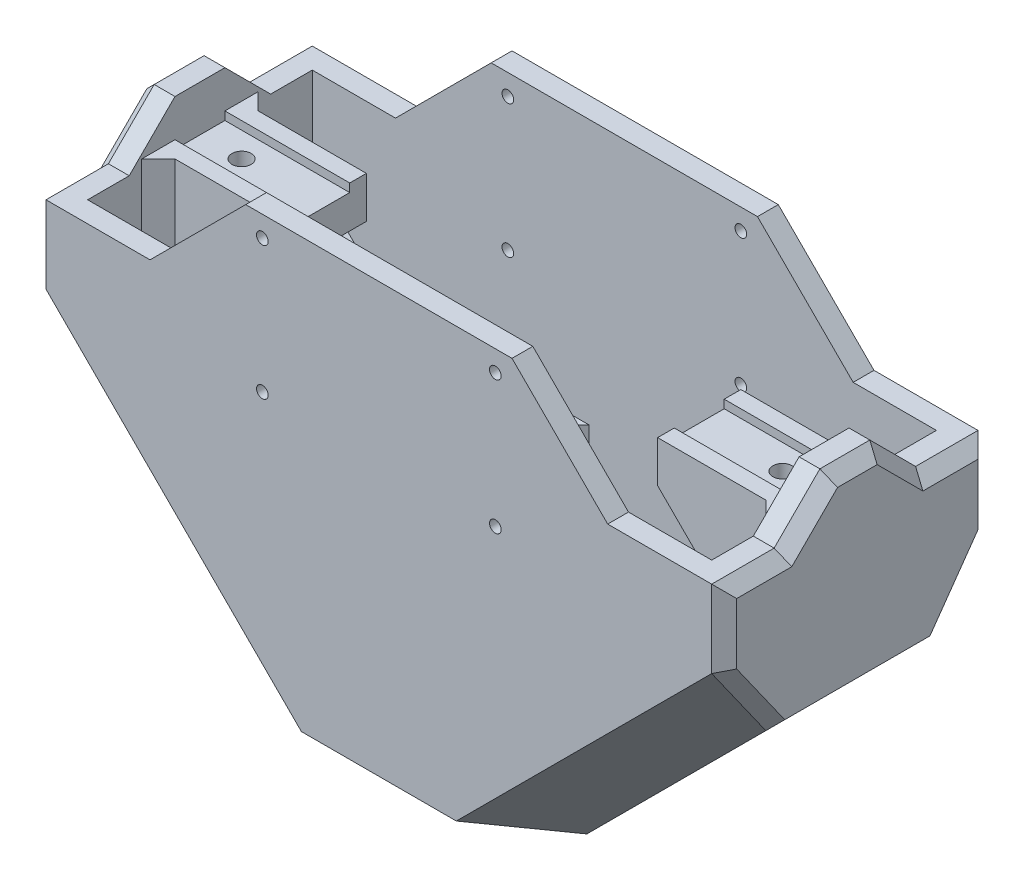
SolidWorks part; units mm, degrees
ref_plane "Front Plane" through (0, 0, 0) normal (0, 0, 1) x (1, 0, 0)
ref_plane "Top Plane" through (0, 0, 0) normal (0, 1, 0) x (1, 0, 0)
ref_plane "Right Plane" through (0, 0, 0) normal (1, 0, 0) x (0, 0, -1)
sketch "Sketch1" plane through (0, 0, 0) normal (0, 1, 0) x (1, 0, 0)
  line L1 (-75, -27) -> (75, -27)
  line L2 (-75, -27) -> (-75, 27)
  line L3 (-75, 27) -> (75, 27)
  line L4 (75, -27) -> (75, 27)
  line L5 (-75, -27) -> (75, 27) construction
  line L6 (-75, 27) -> (75, -27) construction
  point P0 (0, 0)
  dimension "D1" = 150
  dimension "D2" = 54
extrude "Boss-Extrude1" add sketch "Sketch1" along normal blind 75
shell "Shell1" thickness 5
sketch "Sketch2" plane through (80, 0, 0) normal (1, 0, 0) x (0, 0, -1)
  line L0 (-17, 75) -> (-6, 86)
  line L1 (-32, 75) -> (32, 75) construction
  line L2 (-6, 86) -> (6, 86)
  line L3 (6, 86) -> (17, 75)
  line L4 (17, 75) -> (-17, 75)
  line L5 (0, 86) -> (0, 75) construction
  dimension "D1" = 11
  dimension "D2" = 45
  dimension "D3" = 45
  dimension "D4" = 12
extrude "Boss-Extrude2" add sketch "Sketch2" against normal blind 5
sketch "Sketch4" plane through (0, 0, -32) normal (0, 0, -1) x (-1, 0, 0)
  line L0 (-55, 75) -> (-32, 98)
  line L1 (-80, 75) -> (80, 75) construction
  line L2 (-32, 98) -> (32, 98)
  line L3 (32, 98) -> (55, 75)
  line L4 (55, 75) -> (-55, 75)
  line L5 (0, 98) -> (0, 75) construction
  line L6 (-80, 75) -> (-80, -5) construction
  dimension "D1" = 23
  dimension "D2" = 25
  dimension "D3" = 45
extrude "Boss-Extrude3" add sketch "Sketch4" against normal blind 5
sketch "Sketch3" plane through (0, 0, -32) normal (0, 0, -1) x (-1, 0, 0)
  line L1 (-28, 61) -> (28, 61) construction
  line L2 (-28, 61) -> (-28, 93) construction
  line L3 (-28, 93) -> (28, 93) construction
  line L4 (28, 61) -> (28, 93) construction
  line L5 (-28, 61) -> (28, 93) construction
  line L6 (-28, 93) -> (28, 61) construction
  line L7 (32, 98) -> (-32, 98) construction
  circle A0 centre (-28, 93) radius 1.4
  circle A1 centre (-28, 61) radius 1.4
  circle A2 centre (28, 93) radius 1.4
  circle A3 centre (28, 61) radius 1.4
  point P0 (0, 77)
  dimension "D1" = 2.8
  dimension "D2" = 56
  dimension "D3" = 32
  dimension "D4" = 5
extrude "Cut-Extrude1" cut sketch "Sketch3" against normal blind 6
mirror "Mirror4" about plane through (0, 0, 0) normal (0, 0, 1) of "Boss-Extrude3", "Cut-Extrude1"
mirror "Mirror5" about plane through (0, 0, 0) normal (1, 0, 0) of "Boss-Extrude2"
sketch "Sketch5" plane through (0, 0, 0) normal (0, 0, 1) x (1, 0, 0)
  line L0 (-75, 75) -> (-45, 75)
  line L1 (-45, 75) -> (-45, 67)
  line L2 (-45, 67) -> (-75, 37)
  line L4 (-75, 37) -> (-75, 75)
  line L5 (-75, 86) -> (-75, 75) construction
  line L6 (-80, 75) -> (-55, 75) construction
  dimension "D1" = 30
  dimension "D2" = 8
  dimension "D3" = 45
extrude "Boss-Extrude4" add sketch "Sketch5" along normal mid plane 20
sketch "Sketch9" plane through (0, 75, 0) normal (0, 1, 0) x (1, 0, 0)
  line L4 (-45, 10) -> (-75, 10)
  line L5 (-75, 10) -> (-75, -10)
  line L6 (-75, -10) -> (-45, -10)
  line L7 (-45, -10) -> (-45, 10)
  line L8 (-45, 10) -> (-75, 10)
  line L10 (-75, -10) -> (-45, -10)
  line L11 (-45, -10) -> (-45, 10)
  line L13 (-75, 10) -> (-75, -10)
  dimension "D1" = 0
extrude "Boss-Extrude6" add sketch "Sketch9" along normal blind 2
sketch "Sketch10" plane through (-75, 0, 0) normal (1, 0, 0) x (0, 0, -1)
  line L0 (-10, 77) -> (10, 77) construction
  line L1 (-6, 77) -> (6, 77)
  line L2 (-6, 77) -> (-6, 75)
  line L3 (-6, 75) -> (6, 75)
  line L4 (6, 77) -> (6, 75)
  line L5 (-6, 77) -> (6, 75) construction
  line L6 (-6, 75) -> (6, 77) construction
  point P0 (0, 76)
  dimension "D1" = 2
  dimension "D2" = 12
extrude "Cut-Extrude2" cut sketch "Sketch10" along normal up to next
sketch "Sketch11" plane through (0, 75, 0) normal (0, 1, 0) x (1, 0, 0)
  line L1 (-75, 6) -> (-75, -6) construction
  circle A0 centre (-65, 0) radius 2.3
  dimension "D1" = 4.6
  dimension "D2" = 10
extrude "Cut-Extrude3" cut sketch "Sketch11" against normal blind 6
mirror "Mirror24" about plane through (0, 0, 0) normal (1, 0, 0) of "Cut-Extrude2", "Boss-Extrude4", "Boss-Extrude6", "Cut-Extrude3"
sketch "Sketch13" plane through (0, 0, 0) normal (0, 0, 1) x (1, 0, 0)
  line L1 (-21, 16.2) -> (41, 16.2)
  line L2 (-21, 16.2) -> (-21, 31.2)
  line L3 (-21, 31.2) -> (41, 31.2)
  line L4 (41, 16.2) -> (41, 31.2)
  line L5 (-21, 16.2) -> (41, 31.2) construction
  line L6 (-21, 31.2) -> (41, 16.2) construction
  line L11 (-10.5, 31.2) -> (-10.5, 16.2)
  line L12 (30.5, 31.2) -> (30.5, 16.2)
  line L13 (-75, 0) -> (75, 0) construction
  point P0 (10, 23.7)
  dimension "D1" = 62
  dimension "D2" = 15
  dimension "D3" = 31.2
  dimension "D4" = 10
  dimension "D5" = 41
  dimension "D6" = 10.5
extrude "Boss-Extrude8" add sketch "Sketch13" along normal mid plane 54 contours L3 L12 L1 L4 | L11 L3 L2 L1
sketch "Sketch14" plane through (0, 31.2, 0) normal (0, 1, 0) x (1, 0, 0)
  line L0 (-10.5, -27) -> (-10.5, 27) construction
  line L1 (-10.5, -9.6) -> (-15.5, -9.6)
  line L2 (-10.5, -9.6) -> (-10.5, 9.6)
  line L3 (-10.5, 9.6) -> (-15.5, 9.6)
  line L4 (-17.5, -7.6) -> (-17.5, 7.6)
  line L5 (-17.5, 9.6) -> (-10.5, -9.6) construction
  line L10 (-10.5, 27) -> (-21, 27)
  line L11 (-21, 27) -> (-21, -27)
  line L12 (-21, -27) -> (-10.5, -27)
  line L13 (-10.5, -27) -> (-10.5, 27)
  line L14 (-10.5, 27) -> (-21, 27)
  line L15 (-21, 27) -> (-21, -27)
  line L16 (-21, -27) -> (-10.5, -27)
  line L17 (-10.5, -27) -> (-10.5, 27)
  arc A0 (-15.5, -9.6) -> (-17.5, -7.6) centre (-15.5, -7.6) cw
  arc A1 (-15.5, 9.6) -> (-17.5, 7.6) centre (-15.5, 7.6) ccw
  point P6 (-14, 0)
  point P11 (-17.5, -9.6)
  dimension "D3" = 2
  dimension "D1" = 19.2
  dimension "D2" = 7
  dimension "D4" = 0
extrude "Boss-Extrude9" add sketch "Sketch14" along normal blind 3.2
sketch "Sketch15" plane through (0, 31.2, 0) normal (0, 1, 0) x (1, 0, 0)
  line L0 (-14.8, 5) -> (-14.8, -5) construction
  line L1 (-17.5, -7.6) -> (-17.5, 7.6) construction
  circle A0 centre (-14.8, 5) radius 1.4
  circle A1 centre (-14.8, -5) radius 1.4
  point P4 (-14.8, 0)
  dimension "D1" = 10
  dimension "D2" = 2.8
  dimension "D3" = 2.7
extrude "Cut-Extrude4" cut sketch "Sketch15" against normal up to next
chamfer "Chamfer8" distance 0.5 angle 45 2 edges at (-16.2, 31.2, 5) (-16.2, 31.2, -5)
ref_plane "Plane1" through (10, 0, 0) normal (1, 0, 0) x (0, 0, -1)
mirror "Mirror6" about plane through (10, 0, 0) normal (1, 0, 0) of "Chamfer8", "Cut-Extrude4", "Boss-Extrude9"
chamfer "Chamfer3" distance 40 angle 45 2 edges at (75, 0, 0) (-75, 0, 0)
chamfer "Chamfer5" distance 43 angle 45 2 edges at (-80, -5, 0) (80, -5, 0)
chamfer "Chamfer9" distance 5 angle 45 4 edges at (35.75, 16.2, -27) (-15.75, 16.2, -27) (-15.75, 16.2, 27) (35.75, 16.2, 27)
chamfer "Chamfer10" distance 2 angle 45 8 edges at (41, 22.8, -27) (30.5, 22.8, -27) (-10.5, 22.8, -27) (-21, 22.8, -27) (-21, 22.8, 27) (-10.5, 22.8, 27) (30.5, 22.8, 27) (41, 22.8, 27)
chamfer "Chamfer11" distance 10 angle 45 4 edges at (55, 20, 27) (55, 20, -27) (-55, 20, -27) (-55, 20, 27)
chamfer "Chamfer12" distance 13 angle 45 4 edges at (-58.5, 16.5, -32) (58.5, 16.5, -32) (-58.5, 16.5, 32) (58.5, 16.5, 32)
chamfer "Chamfer13" distance 4 angle 45 4 edges at (-75, 58.5, 10) (-75, 58.5, -10) (75, 58.5, 10) (75, 58.5, -10)
sketch "Sketch16" plane through (80, 0, 0) normal (1, 0, 0) x (0, 0, -1)
  line L10 (-19, 38) -> (19, 38)
  line L11 (19, 38) -> (32, 56.3848)
  line L12 (32, 56.3848) -> (32, 75)
  line L13 (32, 75) -> (17, 75)
  line L14 (17, 75) -> (6, 86)
  line L15 (6, 86) -> (-6, 86)
  line L16 (-6, 86) -> (-17, 75)
  line L17 (-17, 75) -> (-32, 75)
  line L18 (-32, 75) -> (-32, 56.3848)
  line L19 (-32, 56.3848) -> (-19, 38)
  line L20 (-19, 38) -> (19, 38)
  line L21 (19, 38) -> (32, 56.3848)
  line L22 (32, 56.3848) -> (32, 75)
  line L23 (32, 75) -> (17, 75)
  line L24 (17, 75) -> (6, 86)
  line L25 (6, 86) -> (-6, 86)
  line L26 (-6, 86) -> (-17, 75)
  line L27 (-17, 75) -> (-32, 75)
  line L28 (-32, 75) -> (-32, 56.3848)
  line L29 (-32, 56.3848) -> (-19, 38)
  dimension "D1" = 0
extrude "Boss-Extrude10" add sketch "Sketch16" along normal blind 3
chamfer "Chamfer14" distance 3 angle 45 10 edges at (83, 65.6924, 32) (83, 75, 24.5) (83, 80.5, 11.5) (83, 86, 0) (83, 80.5, -11.5) (83, 75, -24.5) (83, 65.6924, -32) (83, 47.1924, -25.5) (83, 38, 0) (83, 47.1924, 25.5)
mirror "Mirror28" about plane through (0, 0, 0) normal (1, 0, 0) of "Chamfer14", "Boss-Extrude10"
